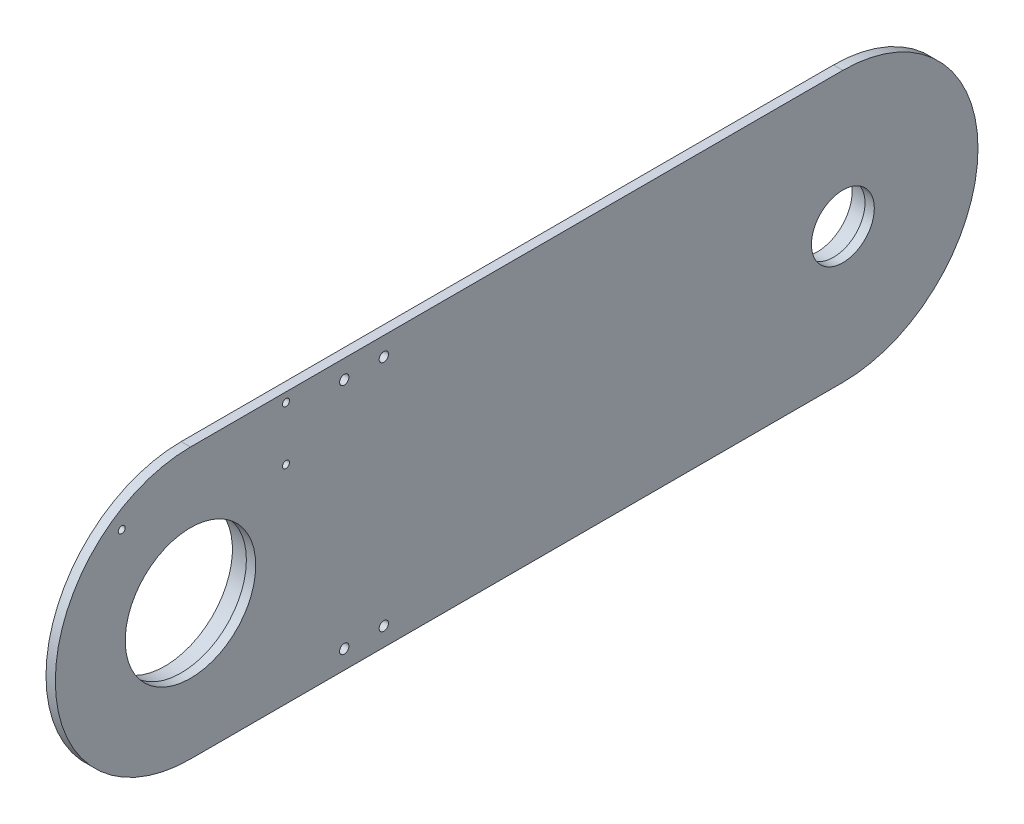
SolidWorks part; units mm, degrees
material "Zoltek Panex 33"
ref_plane "Front Plane" through (0, 0, 0) normal (0, 0, 1) x (1, 0, 0)
ref_plane "Top Plane" through (0, 0, 0) normal (0, 1, 0) x (1, 0, 0)
ref_plane "Right Plane" through (0, 0, 0) normal (1, 0, 0) x (0, 0, -1)
sketch "Sketch1" plane through (0, 0, 0) normal (1, 0, 0) x (0, 0, -1)
  line L0 (0, 0) -> (280, 0) construction
  line L1 (0, 58) -> (280, 58)
  line L2 (0, -58) -> (280, -58)
  arc A0 (0, 58) -> (0, -58) centre (0, 0) ccw
  arc A1 (280, -58) -> (280, 58) centre (280, 0) ccw
  circle A2 centre (0, 0) radius 28
  circle A3 centre (280, 0) radius 13.5
  point P3 (140, 0)
  dimension "D2" = 58
  dimension "D3" = 56
  dimension "D4" = 27
  dimension "D1" = 280
extrude "Boss-Extrude1" add sketch "Sketch1" along normal blind 4
ref_plane "Plane1" through (-7, 0, 0) normal (-1, 0, 0) x (0, 0, 1)
sketch "Sketch2" plane through (-7, 0, 0) normal (-1, 0, 0) x (0, 0, 1)
  line L0 (-140, 58) -> (-140, -58) construction
  line L1 (-280, 58) -> (0, 58) construction
  line L2 (0, -58) -> (-280, -58) construction
  circle A0 centre (0, 0) radius 29
  circle A1 centre (0, 0) radius 34
  circle A2 centre (-280, 0) radius 15
  circle A3 centre (-280, 0) radius 20
  dimension "D1" = 58
  dimension "D2" = 68
  dimension "D3" = 30
  dimension "D4" = 40
extrude "Boss-Extrude2" add sketch "Sketch2" against normal up to surface (7 mm away) up to face at (0, 0, -140)
chamfer "Chamfer1" distance 8 angle 45 2 edges at (0, 0, -34) (0, 0, -300)
sketch "Sketch3" plane through (0, 0, 0) normal (-1, 0, 0) x (0, 0, 1)
  line L0 (0, 58) -> (-73, 58) construction
  line L1 (-280, 58) -> (0, 58) construction
  line L2 (-73, 58) -> (-73, -58) construction
  line L3 (0, -58) -> (-280, -58) construction
  line L4 (-73, 58) -> (-76, 58) construction
  line L5 (-76, 58) -> (-76, -58) construction
  line L6 (-69.0931, 53.5) -> (-66, 53.5) construction
  line L7 (-66, 46.5) -> (-69.0931, 46.5) construction
  line L8 (-66, 50) -> (-73, 50) construction
  line L9 (-73, 55.8533) -> (-73, 44.1467) construction
  line L10 (-73, 0) -> (-99.886, 0) construction
  line L11 (-74.5, 58) -> (-74.5, 37.4458) construction
  arc A0 (-69.0931, 53.5) -> (-73, 55.8533) centre (-69.0931, 57.9197) cw construction
  arc A1 (-66, 53.5) -> (-66, 46.5) centre (-66, 50) cw construction
  arc A2 (-69.0931, 46.5) -> (-73, 44.1467) centre (-69.0931, 42.0803) ccw construction
  circle A3 centre (-66, 50) radius 2
  circle A4 centre (-66, -50) radius 2
  circle A5 centre (-83, -50) radius 2
  circle A6 centre (-83, 50) radius 2
  dimension "D3" = 4
  dimension "D1" = 73
  dimension "D2" = 3
  dimension "D4" = 7
  dimension "D5" = 8
  dimension "D6" = 7
extrude "Cut-Extrude1" cut sketch "Sketch3" against normal through all contours A3 | A4 | A6 | A5
sketch "Sketch4" plane through (4, 0, 0) normal (1, 0, 0) x (0, 0, -1)
  line L0 (0, 58) -> (73, 58) construction
  line L1 (280, 58) -> (0, 58) construction
  line L2 (73, 58) -> (73, 42) construction
  line L3 (73, 42) -> (-29.5, 42) construction
  line L4 (73, 58) -> (73, 54) construction
  line L5 (73, 54) -> (41, 54) construction
  line L6 (41, 54) -> (41, 31) construction
  circle A0 centre (-29.5, 42) radius 1.5
  circle A1 centre (41, 54) radius 1.5
  circle A2 centre (41, 31) radius 1.5
  dimension "D4" = 3
  dimension "D8" = 3
  dimension "D9" = 3
  dimension "D1" = 73
  dimension "D2" = 16
  dimension "D3" = 102.5
  dimension "D5" = 4
  dimension "D6" = 32
  dimension "D7" = 23
extrude "Cut-Extrude2" cut sketch "Sketch4" against normal through all
sketch "Sketch5" plane through (-7, 0, 0) normal (-1, 0, 0) x (0, 0, 1)
  line L0 (-280, 0) -> (-280, 17) construction
  circle A0 centre (-280, 17) radius 1.5
  circle A1 centre (-263, 0) radius 1.5
  circle A2 centre (-280, -17) radius 1.5
  circle A3 centre (-297, 0) radius 1.5
  point P5 (-298.578, 2.9455)
  point P6 (0, 0)
  point P12 (-280, 0)
  dimension "D2" = 3
  dimension "D1" = 17
  dimension "D3" = 4
extrude "Cut-Extrude3" cut sketch "Sketch5" against normal blind 5
equation "\"mini-flipper-shaft-diameter\"= 26mm"
equation "\"mini-shaft-ring-groove-diam\"= 7.8mm"
equation "\"mini-shaft-ring-groove-width\"= 1mm"
equation "\"dtCoverPlate-DistFrom-GearCent\"= 73mm"
equation "\"wormGearShaft-L\"= \"dtCoverPlate-DistFrom-GearCent\" - 27.75 + 3.75"
equation "\"D1@Sketch3\"=\"dtCoverPlate-DistFrom-GearCent\""
